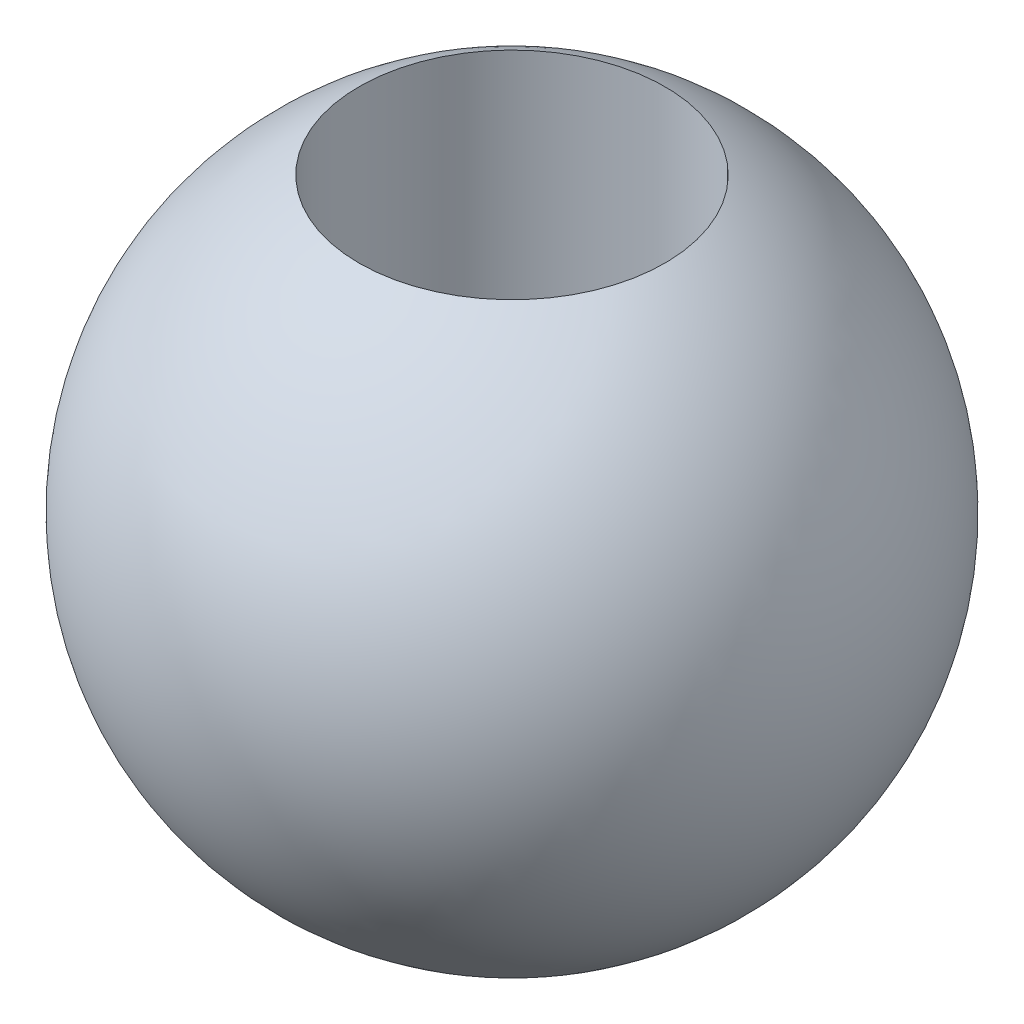
SolidWorks part; units mm, degrees
ref_plane "Front Plane" through (0, 0, 0) normal (0, 0, 1) x (1, 0, 0)
ref_plane "Top Plane" through (0, 0, 0) normal (0, 1, 0) x (1, 0, 0)
ref_plane "Right Plane" through (0, 0, 0) normal (1, 0, 0) x (0, 0, -1)
sketch "Sketch2" plane through (0, 0, 0) normal (1, 0, 0) x (0, 0, -1)
  line L0 (0, -1000) -> (0, 49000) construction
  line L2 (-1.4732, -2.8125) -> (-1.4732, 2.8125)
  arc A0 (-1.4732, -2.8125) -> (-1.4732, 2.8125) centre (0, 0) cw
  dimension "D1" = 3.175
  dimension "D2" = 1.4732
revolve "Revolve1" add sketch "Sketch2" angle 360 about L0
